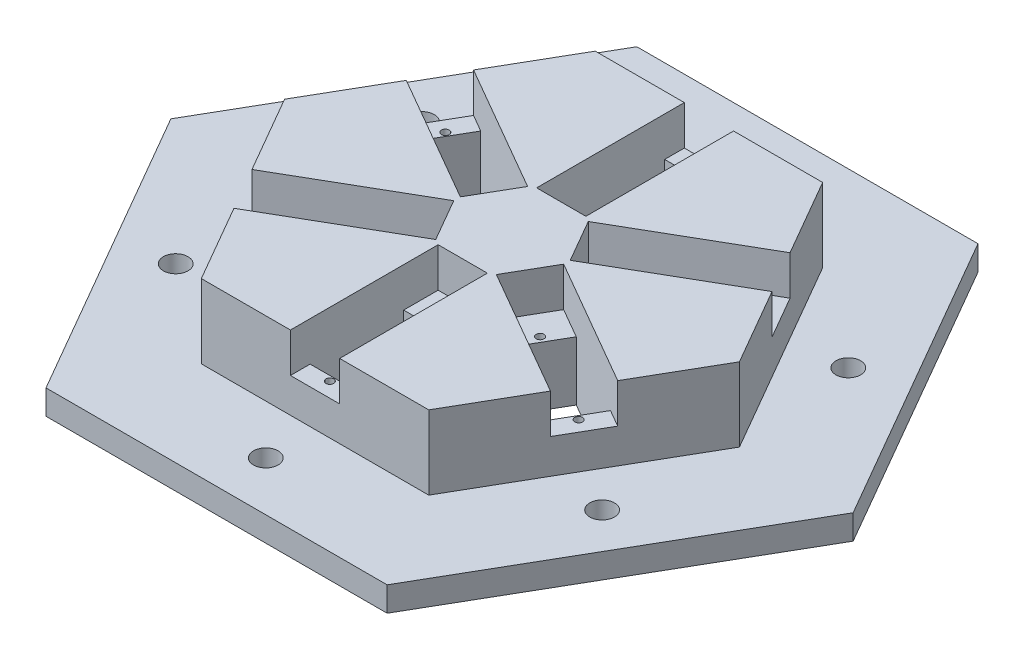
SolidWorks part; units mm, degrees
ref_plane "Front Plane" through (0, 0, 0) normal (0, 0, 1) x (1, 0, 0)
ref_plane "Top Plane" through (0, 0, 0) normal (0, 1, 0) x (1, 0, 0)
ref_plane "Right Plane" through (0, 0, 0) normal (1, 0, 0) x (0, 0, -1)
sketch "Sketch1" plane through (0, 0, 0) normal (0, 1, 0) x (1, 0, 0)
  line L0 (0, 0) -> (58.6588, 0) construction
  line L1 (58.6588, 0) -> (29.3294, 50.8)
  line L2 (29.3294, 50.8) -> (-29.3294, 50.8)
  line L3 (-29.3294, 50.8) -> (-58.6588, 0)
  line L4 (-58.6588, 0) -> (-29.3294, -50.8)
  line L5 (-29.3294, -50.8) -> (29.3294, -50.8)
  line L6 (29.3294, -50.8) -> (58.6588, 0)
  circle A0 centre (0, 0) radius 50.8 construction
  dimension "D1" = 101.6
extrude "Boss-Extrude1" add sketch "Sketch1" along normal blind 25.4
sketch "Sketch5" plane through (0, 0, 0) normal (0, -1, 0) x (1, 0, 0)
  line L0 (0, -50.8) -> (0, -76.2) construction
  line L1 (87.9882, 0) -> (43.9941, 76.2)
  line L2 (43.9941, 76.2) -> (-43.9941, 76.2)
  line L3 (-43.9941, 76.2) -> (-87.9882, 0)
  line L4 (-87.9882, 0) -> (-43.9941, -76.2)
  line L5 (-43.9941, -76.2) -> (43.9941, -76.2)
  line L6 (43.9941, -76.2) -> (87.9882, 0)
  line L7 (29.3294, -50.8) -> (-29.3294, -50.8) construction
  line L14 (58.6588, 0) -> (29.3294, 50.8)
  line L15 (29.3294, 50.8) -> (-29.3294, 50.8)
  line L16 (-29.3294, 50.8) -> (-58.6588, 0)
  line L17 (-58.6588, 0) -> (-29.3294, -50.8)
  line L18 (-29.3294, -50.8) -> (29.3294, -50.8)
  line L19 (29.3294, -50.8) -> (58.6588, 0)
  line L20 (58.6588, 0) -> (29.3294, 50.8)
  line L21 (29.3294, 50.8) -> (-29.3294, 50.8)
  line L22 (-29.3294, 50.8) -> (-58.6588, 0)
  line L23 (-58.6588, 0) -> (-29.3294, -50.8)
  line L24 (-29.3294, -50.8) -> (29.3294, -50.8)
  line L25 (29.3294, -50.8) -> (58.6588, 0)
  circle A0 centre (0, 0) radius 76.2 construction
  dimension "D1" = 25.4
  dimension "D2" = 0
extrude "Boss-Extrude2" add sketch "Sketch5" against normal blind 6.35
sketch "Sketch2" plane through (0, 25.4, 0) normal (0, 1, 0) x (1, 0, 0)
  line L0 (-29.3294, -50.8) -> (29.3294, -50.8) construction
  line L1 (-6.35, -12.7) -> (6.35, -12.7)
  line L2 (-6.35, -12.7) -> (-6.35, -50.8)
  line L3 (-6.35, -50.8) -> (6.35, -50.8)
  line L4 (6.35, -12.7) -> (6.35, -50.8)
  line L5 (-6.35, -12.7) -> (6.35, -50.8) construction
  line L6 (-6.35, -50.8) -> (6.35, -12.7) construction
  line L7 (0, 0) -> (0, -31.75) construction
  point P0 (0, -31.75)
  dimension "D1" = 12.7
  dimension "D2" = 38.1
extrude "Cut-Extrude1" cut sketch "Sketch2" against normal blind 10.16
sketch "Sketch3" plane through (0, 15.24, 0) normal (0, 1, 0) x (1, 0, 0)
  line L0 (6.35, -50.8) -> (6.35, -12.7) construction
  line L1 (-6.35, -21.59) -> (6.35, -21.59)
  line L2 (-6.35, -21.59) -> (-6.35, -45.72)
  line L3 (-6.35, -45.72) -> (6.35, -45.72)
  line L4 (6.35, -21.59) -> (6.35, -45.72)
  line L5 (-6.35, -21.59) -> (6.35, -45.72) construction
  line L6 (-6.35, -45.72) -> (6.35, -21.59) construction
  line L7 (-6.35, -50.8) -> (6.35, -50.8) construction
  line L8 (-6.35, -12.7) -> (-6.35, -50.8) construction
  point P0 (0, -33.655)
  dimension "D1" = 5.08
  dimension "D2" = 24.13
extrude "Cut-Extrude2" cut sketch "Sketch3" against normal through all
sketch "Sketch4" plane through (0, 15.24, 0) normal (0, 1, 0) x (1, 0, 0)
  line L0 (0, -19.812) -> (0, -46.99) construction
  line L1 (0, -46.99) -> (0, -50.8) construction
  line L2 (-6.35, -50.8) -> (6.35, -50.8) construction
  line L3 (-6.35, -45.72) -> (6.35, -45.72) construction
  circle A0 centre (0, -19.812) radius 1.016
  circle A1 centre (0, -46.99) radius 1.016
  dimension "D3" = 2.032
  dimension "D1" = 27.178
  dimension "D2" = 1.27
extrude "Cut-Extrude3" cut sketch "Sketch4" against normal blind 12.7
sketch "Sketch6" plane through (0, 6.35, 0) normal (0, 1, 0) x (1, 0, 0)
  line L0 (0, -63.5) -> (0, 0) construction
  line L2 (29.3294, -50.8) -> (-29.3294, -50.8) construction
  circle A0 centre (0, -63.5) radius 3.175
  point P2 (0, -60.1903)
  dimension "D1" = 6.35
  dimension "D2" = 12.7
extrude "Cut-Extrude4" cut sketch "Sketch6" against normal through all
ref_axis "Axis1" through (0, 26.67, 0) along (0, -1, 0)
pattern_circular "CirPattern1" count 6 over 360 about axis through (0, 26.67, 0) along (0, -1, 0) of "Cut-Extrude1", "Cut-Extrude2", "Cut-Extrude3", "Cut-Extrude4"
